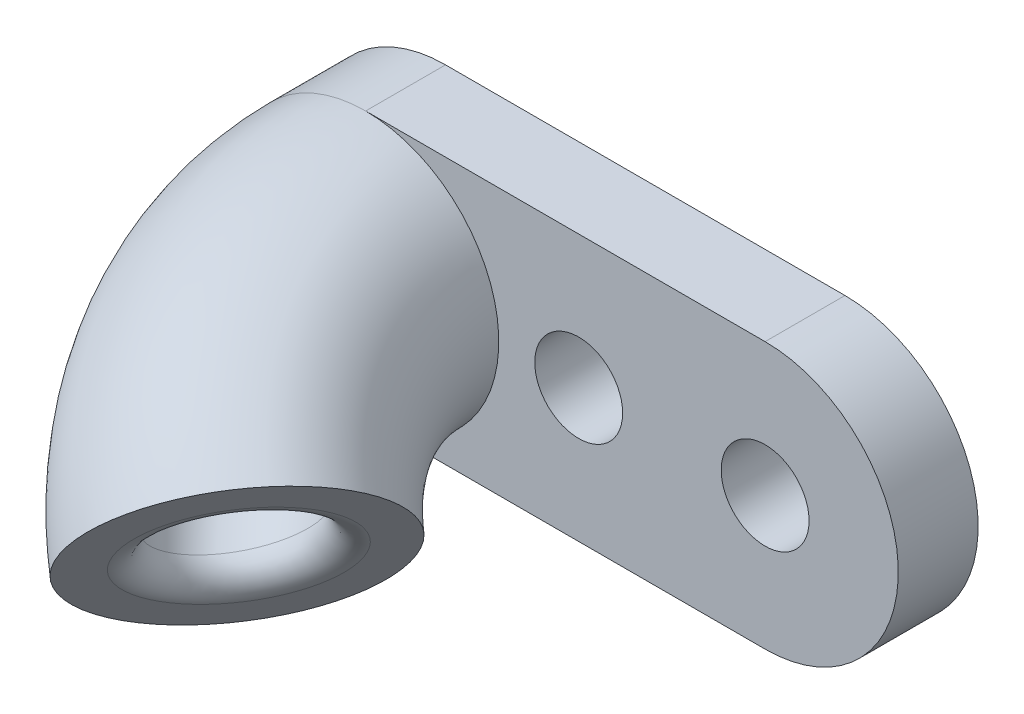
SolidWorks part; units mm, degrees
ref_plane "正面(Front)" through (0, 0, 0) normal (0, 0, 1) x (1, 0, 0)
ref_plane "平面(Top)" through (0, 0, 0) normal (0, 1, 0) x (1, 0, 0)
ref_plane "右側面(Right)" through (0, 0, 0) normal (1, 0, 0) x (0, 0, -1)
sketch "ｽｹｯﾁ1" plane through (0, 0, 0) normal (0, 0, 1) x (1, 0, 0)
  line L0 (0, 0) -> (15, 0) construction
  line L1 (0, 5) -> (15, 5)
  line L2 (0, -5) -> (15, -5)
  circle A0 centre (0, 0) radius 2.5
  arc A1 (0, 5) -> (0, -5) centre (0, 0) ccw
  arc A2 (15, -5) -> (15, 5) centre (15, 0) ccw
  point P3 (7.5, 0)
  dimension "D3" = 5
  dimension "D1" = 10
  dimension "D2" = 15
extrude "ﾎﾞｽ - 押し出し1" add sketch "ｽｹｯﾁ1" against normal blind 3
sketch "ｽｹｯﾁ3" plane through (0, 0, 0) normal (1, 0, 0) x (0, 0, -1)
  line L0 (-10.6066, -4.3934) -> (0, -15) construction
  line L1 (0, 5) -> (0, -5) construction
  arc A0 (0, 0) -> (-10.6066, -4.3934) centre (0, -15) ccw
  dimension "D2" = 15
  dimension "D1" = 45
ref_axis "軸1" through (0, 0, -3.15) along (0, 0, 1)
ref_plane "平面1" through (0, 0, 0) normal (0.6428, 0.766, 0) x (0, 0, 1)
sketch "ｽｹｯﾁ6" plane through (0, 0, 0) normal (0.6428, 0.766, 0) x (0, 0, 1)
  line L0 (0, 10) -> (8.6603, 5) construction
  line L1 (0, 8.2767) -> (0, -3.2139) construction
  arc A0 (0, 0) -> (8.6603, 5) centre (0, 10) ccw
  dimension "D2" = 10
  dimension "D1" = 60
sketch "ｽｹｯﾁ4" plane through (0, 0, 0) normal (0, 0, 1) x (1, 0, 0)
  circle A0 centre (0, 0) radius 2.5 construction
  circle A1 centre (0, 0) radius 2.5
  arc A2 (0, 5) -> (0, -5) centre (0, 0) ccw construction
  circle A3 centre (0, 0) radius 5
sweep "ｽｲｰﾌﾟ1" add profiles "ｽｹｯﾁ4" path "ｽｹｯﾁ6"
sketch "ｽｹｯﾁ5" plane through (0, 0, 0) normal (0, 0, 1) x (1, 0, 0)
  line L0 (0, 0) -> (21.6264, 0) construction
  circle A0 centre (8, 0) radius 1.65
  circle A1 centre (15, 0) radius 1.65
  dimension "D1" = 8
  dimension "D2" = 7
  dimension "D3" = 3.3
extrude "ｶｯﾄ - 押し出し1" cut sketch "ｽｹｯﾁ5" against normal through all
fillet "ﾌｨﾚｯﾄ1" radius 1 1 edges at (5.5967, -2.5984, 7.0017)
